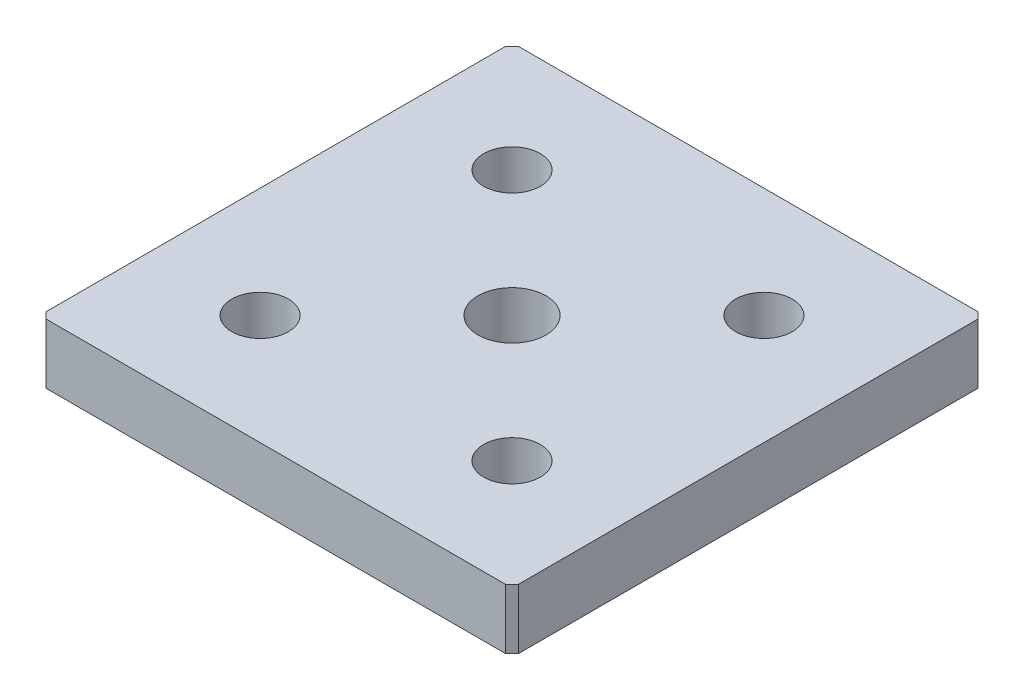
SolidWorks part; units mm, degrees
material "6061-T6 (SS)"
ref_plane "Front Plane" through (0, 0, 0) normal (0, 0, 1) x (1, 0, 0)
ref_plane "Top Plane" through (0, 0, 0) normal (0, 1, 0) x (1, 0, 0)
ref_plane "Right Plane" through (0, 0, 0) normal (1, 0, 0) x (0, 0, -1)
sketch "Sketch1" plane through (0, 0, 0) normal (0, 1, 0) x (1, 0, 0)
  line L1 (-37.5, 37.5) -> (37.5, 37.5)
  line L2 (-37.5, 37.5) -> (-37.5, -37.5)
  line L3 (-37.5, -37.5) -> (37.5, -37.5)
  line L4 (37.5, 37.5) -> (37.5, -37.5)
  line L5 (-37.5, 37.5) -> (37.5, -37.5) construction
  line L6 (-37.5, -37.5) -> (37.5, 37.5) construction
  point P0 (0, 0)
  dimension "D1" = 75
  dimension "D2" = 75
extrude "Boss-Extrude1" add sketch "Sketch1" along normal mid plane 9.525
hole_wizard "M8 Clearance Hole1" positions "Sketch2" profile "Sketch3" hole size "M8" standard "ANSI Metric" end condition through all
sketch "Sketch2" plane through (0, 4.7625, 0) normal (0, 1, 0) x (1, 0, 0)
  line L0 (20, 20) -> (-20, 20)
  line L2 (20, 20) -> (20, -20)
  line L3 (20, -20) -> (-20, -20)
  line L4 (-20, -20) -> (-20, 20)
  line L6 (-20, 20) -> (20, -20)
  point P0 (-20, 20)
  point P2 (20, 20)
  point P22 (-20, -20)
  point P25 (20, -20)
  dimension "D1" = 40
sketch "Sketch3" plane through (-20, 4.7625, -20) normal (1, 0, 0) x (0, 0, 1)
  line L0 (0, 0) -> (0, 9.525)
  line L1 (0, 9.525) -> (4.5, 9.525)
  line L2 (4.5, 9.525) -> (4.5, 0)
  line L5 (4.5, 0) -> (0, 0)
  line L11 (0, -6.35) -> (0, 107.95) construction
  dimension "Thru Hole Dia." = 9
  dimension "Thru Hole Depth" = 9.525
hole_wizard "M12x1.25 Tapped Hole1" positions "Sketch4" profile "Sketch5" tap size "M12x1.25" standard "ANSI Metric" end condition through all
sketch "Sketch4" plane through (0, 4.7625, 0) normal (0, 1, 0) x (1, 0, 0)
  point P0 (0, 0)
sketch "Sketch5" plane through (0, 4.7625, 0) normal (1, 0, 0) x (0, 0, 1)
  line L0 (0, 0) -> (0, 9.525)
  line L1 (0, 9.525) -> (5.4, 9.525)
  line L2 (5.4, 9.525) -> (5.4, 0)
  line L5 (5.4, 0) -> (0, 0)
  line L11 (0, -6.35) -> (0, 107.95) construction
  dimension "Thru Tap Drill Dia." = 10.8
  dimension "Thru Tap Drill Depth" = 9.525
cosmetic thread "Hole Thread1" parameters "D2"=12
chamfer "Chamfer1" distance 1 angle 45 4 edges at (37.5, 0, -37.5) (37.5, 0, 37.5) (-37.5, 0, 37.5) (-37.5, 0, -37.5)
